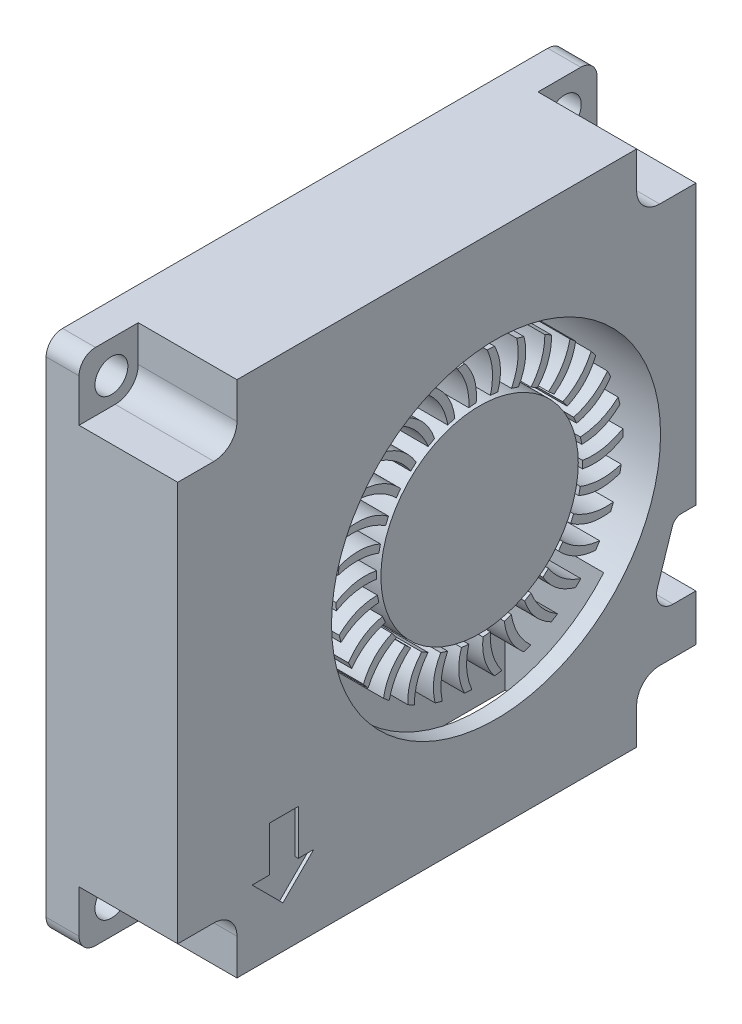
SolidWorks part; units mm, degrees
material "PPE"
ref_plane "Front Plane" through (0, 0, 0) normal (1, 0, 0) x (0, 1, 0)
ref_plane "Top Plane" through (0, 0, 0) normal (0, 0, 1) x (0, 1, 0)
ref_plane "Right Plane" through (0, 0, 0) normal (0, 1, 0) x (-1, 0, 0)
sketch "Sketch1" plane through (0, 0, 0) normal (1, 0, 0) x (0, 1, 0)
  line L1 (-18.73, -20) -> (18.73, -20)
  line L2 (-20, -18.73) -> (-20, 18.73)
  line L3 (-18.73, 20) -> (18.73, 20)
  line L4 (20, -18.73) -> (20, 18.73)
  line L5 (-20, -20) -> (20, 20) construction
  line L6 (-20, 20) -> (20, -20) construction
  arc A0 (-18.73, -20) -> (-20, -18.73) centre (-18.73, -18.73) cw
  arc A1 (-20, 18.73) -> (-18.73, 20) centre (-18.73, 18.73) cw
  arc A2 (18.73, -20) -> (20, -18.73) centre (18.73, -18.73) ccw
  arc A3 (18.73, 20) -> (20, 18.73) centre (18.73, 18.73) cw
  point P0 (0, 0)
  dimension "D2" = 1.27
  dimension "D1" = 40
extrude "Boss-Extrude1" add sketch "Sketch1" along normal blind 10.16
sketch "Sketch2" plane through (10.16, 0, 0) normal (1, 0, 0) x (0, 1, 0)
  line L2 (-20, 18.73) -> (-20, -18.73) construction
  line L3 (-24.572, 24.572) -> (-15.428, 24.572)
  line L4 (-24.572, 24.572) -> (-24.572, 15.428)
  line L5 (-24.572, 15.428) -> (-17.206, 15.428)
  line L6 (-15.428, 24.572) -> (-15.428, 17.206)
  line L7 (-24.572, 24.572) -> (-15.428, 15.428) construction
  line L8 (-24.572, 15.428) -> (-15.428, 24.572) construction
  line L9 (18.73, 20) -> (-18.73, 20) construction
  line L10 (24.572, 24.572) -> (15.428, 24.572)
  line L11 (24.572, 24.572) -> (24.572, 15.428)
  line L12 (24.572, 15.428) -> (17.206, 15.428)
  line L13 (15.428, 24.572) -> (15.428, 17.206)
  line L14 (24.572, -24.572) -> (24.572, -15.428)
  line L15 (24.572, -24.572) -> (15.428, -24.572)
  line L16 (15.428, -24.572) -> (15.428, -17.206)
  line L17 (24.572, -15.428) -> (17.206, -15.428)
  line L18 (-24.572, -24.572) -> (-15.428, -24.572)
  line L19 (-24.572, -24.572) -> (-24.572, -15.428)
  line L20 (-24.572, -15.428) -> (-17.206, -15.428)
  line L21 (-15.428, -24.572) -> (-15.428, -17.206)
  arc A4 (-17.206, 15.428) -> (-15.428, 17.206) centre (-17.206, 17.206) ccw
  arc A5 (15.428, 17.206) -> (17.206, 15.428) centre (17.206, 17.206) ccw
  arc A6 (17.206, -15.428) -> (15.428, -17.206) centre (17.206, -17.206) ccw
  arc A7 (-15.428, -17.206) -> (-17.206, -15.428) centre (-17.206, -17.206) ccw
  point P0 (-20, 20)
  point P5 (0, 0)
  point P15 (0, 0)
  point P35 (0, 0)
  dimension "D1" = 4.572
  dimension "D3" = 1.778
  dimension "D2" = 4.572
  dimension "D4" = 4
extrude "Cut-Extrude1" cut sketch "Sketch2" against normal blind 7.62
sketch "Sketch3" plane through (10.16, 0, 0) normal (1, 0, 0) x (0, 1, 0)
  circle A0 centre (0, -4.572) radius 12.7
  point P2 (-1.9961, -4.964)
  dimension "D3" = 25.4
  dimension "D1" = 4.572
  dimension "D2" = 0
extrude "Cut-Extrude2" cut sketch "Sketch3" against normal blind 8.89
sketch "Sketch4" plane through (0, -20, 0) normal (0, -1, 0) x (1, 0, 0)
  line L0 (10.16, 15.428) -> (10.16, -15.428) construction
  line L1 (1.27, 14.158) -> (8.89, 14.158)
  line L2 (1.27, 14.158) -> (1.27, -14.158)
  line L3 (1.27, -14.158) -> (8.89, -14.158)
  line L4 (8.89, 14.158) -> (8.89, -14.158)
  line L5 (0, 18.73) -> (0, -18.73) construction
  line L8 (10.16, 15.428) -> (2.54, 15.428) construction
  line L9 (2.54, -15.428) -> (10.16, -15.428) construction
  dimension "D1" = 1.27
  dimension "D2" = 1.27
  dimension "D3" = 1.27
  dimension "D4" = 1.27
extrude "Cut-Extrude3" cut sketch "Sketch4" against normal blind 36.576
sketch "Sketch5" plane through (1.27, 0, 0) normal (1, 0, 0) x (0, 1, 0)
  circle A0 centre (0, -4.572) radius 11.43
  dimension "D1" = 22.86
extrude "Boss-Extrude2" add sketch "Sketch5" along normal blind 1.27
sketch "Sketch6" plane through (2.54, 0, 0) normal (1, 0, 0) x (0, 1, 0)
  line L60 (-0.5633, 6.4855) -> (0, 6.507)
  line L61 (0, 3.375) -> (0.574, 3.375)
  line L62 (1.6523, 3.2014) -> (2.2137, 3.082)
  line L63 (1.748, 6.3609) -> (2.3035, 6.2649)
  line L64 (3.2324, 2.688) -> (3.7567, 2.4545)
  line L65 (3.9829, 5.7586) -> (4.5062, 5.5492)
  line L66 (4.6712, 1.8573) -> (5.1355, 1.5199)
  line L67 (6.0437, 4.7048) -> (6.5121, 4.3911)
  line L68 (5.9058, 0.7456) -> (6.2899, 0.3191)
  line L69 (7.8404, 3.2455) -> (8.2333, 2.8413)
  line L70 (6.8823, -0.5985) -> (7.1693, -1.0955)
  line L71 (9.2944, 1.4445) -> (9.5947, 0.9675)
  line L72 (7.5581, -2.1162) -> (7.7354, -2.6621)
  line L73 (10.3422, -0.6193) -> (10.5367, -1.1484)
  line L74 (7.9035, -3.7413) -> (7.9635, -4.3121)
  line L75 (10.938, -2.856) -> (11.0183, -3.4139)
  line L76 (7.9035, -5.4027) -> (7.8435, -5.9735)
  line L77 (11.0558, -5.1676) -> (11.0183, -5.7301)
  line L78 (7.5581, -7.0278) -> (7.3807, -7.5736)
  line L79 (10.6903, -7.4532) -> (10.5367, -7.9956)
  line L80 (6.8823, -8.5455) -> (6.5954, -9.0426)
  line L81 (9.8577, -9.6129) -> (9.5947, -10.1115)
  line L82 (5.9058, -9.8896) -> (5.5218, -10.3161)
  line L83 (8.5942, -11.5523) -> (8.2333, -11.9853)
  line L84 (4.6712, -11.0013) -> (4.2068, -11.3387)
  line L85 (6.9551, -13.1866) -> (6.5121, -13.5351)
  line L86 (3.2324, -11.832) -> (2.708, -12.0654)
  line L87 (5.0121, -14.4444) -> (4.5062, -14.6932)
  line L88 (1.6523, -12.3454) -> (1.0909, -12.4647)
  line L89 (2.8499, -15.2707) -> (2.3035, -15.4089)
  line L90 (0, -12.519) -> (-0.574, -12.519)
  line L91 (0.5633, -15.6295) -> (0, -15.651)
  line L92 (-1.6523, -12.3454) -> (-2.2137, -12.226)
  line L93 (-1.748, -15.5049) -> (-2.3035, -15.4089)
  line L94 (-3.2324, -11.832) -> (-3.7567, -11.5985)
  line L95 (-3.9829, -14.9026) -> (-4.5062, -14.6932)
  line L96 (-4.6712, -11.0013) -> (-5.1355, -10.6639)
  line L97 (-6.0437, -13.8488) -> (-6.5121, -13.5351)
  line L98 (-5.9058, -9.8896) -> (-6.2899, -9.4631)
  line L99 (-7.8404, -12.3895) -> (-8.2333, -11.9853)
  line L100 (-6.8823, -8.5455) -> (-7.1693, -8.0485)
  line L101 (-9.2944, -10.5885) -> (-9.5947, -10.1115)
  line L102 (-7.5581, -7.0278) -> (-7.7354, -6.4819)
  line L103 (-10.3422, -8.5247) -> (-10.5367, -7.9956)
  line L104 (-7.9035, -5.4027) -> (-7.9635, -4.8319)
  line L105 (-10.938, -6.288) -> (-11.0183, -5.7301)
  line L106 (-7.9035, -3.7413) -> (-7.8435, -3.1705)
  line L107 (-11.0558, -3.9764) -> (-11.0183, -3.4139)
  line L108 (-7.5581, -2.1162) -> (-7.3807, -1.5704)
  line L109 (-10.6903, -1.6908) -> (-10.5367, -1.1484)
  line L110 (-6.8823, -0.5985) -> (-6.5954, -0.1014)
  line L111 (-9.8577, 0.4689) -> (-9.5947, 0.9675)
  line L112 (-5.9058, 0.7456) -> (-5.5218, 1.1721)
  line L113 (-8.5942, 2.4083) -> (-8.2333, 2.8413)
  line L114 (-4.6712, 1.8573) -> (-4.2068, 2.1947)
  line L115 (-6.9551, 4.0426) -> (-6.5121, 4.3911)
  line L116 (-3.2324, 2.688) -> (-2.708, 2.9214)
  line L117 (-5.0121, 5.3004) -> (-4.5062, 5.5492)
  line L118 (-1.6523, 3.2014) -> (-1.0909, 3.3207)
  line L119 (-2.8499, 6.1267) -> (-2.3035, 6.2649)
  circle A3 centre (0, -4.572) radius 7.62
  circle A4 centre (0, -4.572) radius 11.43 construction
  spline S0 degree 2 poles (0, 3.375) (0.2617, 5.0251) (-0.5633, 6.4855) knots 0 0 0 1 1 1
  spline S1 degree 2 poles (0.574, 3.375) (0.9192, 5.0579) (0, 6.507) knots 0 0 0 1 1 1
  spline S2 degree 2 poles (2.2137, 3.082) (2.9012, 4.6563) (2.3035, 6.2649) knots 0 0 0 1 1 1
  spline S3 degree 2 poles (1.6523, 3.2014) (2.2513, 4.7609) (1.748, 6.3609) knots 0 0 0 1 1 1
  spline S4 degree 2 poles (3.7567, 2.4545) (4.7565, 3.8515) (4.5062, 5.5492) knots 0 0 0 1 1 1
  spline S5 degree 2 poles (3.2324, 2.688) (4.1425, 4.0889) (3.9829, 5.7586) knots 0 0 0 1 1 1
  spline S6 degree 2 poles (5.1355, 1.5199) (6.4039, 2.6784) (6.5121, 4.3911) knots 0 0 0 1 1 1
  spline S7 degree 2 poles (4.6712, 1.8573) (5.8527, 3.0384) (6.0437, 4.7048) knots 0 0 0 1 1 1
  spline S8 degree 2 poles (6.2899, 0.3191) (7.7714, 1.1886) (8.2333, 2.8413) knots 0 0 0 1 1 1
  spline S9 degree 2 poles (5.9058, 0.7456) (7.3071, 1.6552) (7.8404, 3.2455) knots 0 0 0 1 1 1
  spline S10 degree 2 poles (7.1693, -1.0955) (8.7993, -0.5531) (9.5947, 0.9675) knots 0 0 0 1 1 1
  spline S11 degree 2 poles (6.8823, -0.5985) (8.4421, -0.0001) (9.2944, 1.4445) knots 0 0 0 1 1 1
  spline S12 degree 2 poles (7.7354, -2.6621) (9.4426, -2.4704) (10.5367, -1.1484) knots 0 0 0 1 1 1
  spline S13 degree 2 poles (7.5581, -2.1162) (9.2082, -1.8552) (10.3422, -0.6193) knots 0 0 0 1 1 1
  spline S14 degree 2 poles (7.9635, -4.3121) (9.6732, -4.4795) (11.0183, -3.4139) knots 0 0 0 1 1 1
  spline S15 degree 2 poles (7.9035, -3.7413) (9.5718, -3.8291) (10.938, -2.856) knots 0 0 0 1 1 1
  spline S16 degree 2 poles (7.8435, -5.9735) (9.481, -6.4927) (11.0183, -5.7301) knots 0 0 0 1 1 1
  spline S17 degree 2 poles (7.9035, -5.4027) (9.5171, -5.8354) (11.0558, -5.1676) knots 0 0 0 1 1 1
  spline S18 degree 2 poles (7.3807, -7.5736) (8.8745, -8.422) (10.5367, -7.9956) knots 0 0 0 1 1 1
  spline S19 degree 2 poles (7.5581, -7.0278) (9.0465, -7.7865) (10.6903, -7.4532) knots 0 0 0 1 1 1
  spline S20 degree 2 poles (6.5954, -9.0426) (7.8801, -10.1829) (9.5947, -10.1115) knots 0 0 0 1 1 1
  spline S21 degree 2 poles (6.8823, -8.5455) (8.1805, -9.5972) (9.8577, -9.6129) knots 0 0 0 1 1 1
  spline S22 degree 2 poles (5.5218, -10.3161) (6.5413, -11.6987) (8.2333, -11.9853) knots 0 0 0 1 1 1
  spline S23 degree 2 poles (5.9058, -9.8896) (6.9569, -11.1882) (8.5942, -11.5523) knots 0 0 0 1 1 1
  spline S24 degree 2 poles (4.2068, -11.3387) (4.9167, -12.903) (6.5121, -13.5351) knots 0 0 0 1 1 1
  spline S25 degree 2 poles (4.6712, -11.0013) (5.4293, -12.49) (6.9551, -13.1866) knots 0 0 0 1 1 1
  spline S26 degree 2 poles (2.708, -12.0654) (3.0771, -13.7432) (4.5062, -14.6932) knots 0 0 0 1 1 1
  spline S27 degree 2 poles (3.2324, -11.832) (3.6644, -13.4458) (5.0121, -14.4444) knots 0 0 0 1 1 1
  spline S28 degree 2 poles (1.0909, -12.4647) (1.1031, -14.1825) (2.3035, -15.4089) knots 0 0 0 1 1 1
  spline S29 degree 2 poles (1.6523, -12.3454) (1.7394, -14.0137) (2.8499, -15.2707) knots 0 0 0 1 1 1
  spline S30 degree 2 poles (-0.574, -12.519) (-0.9192, -14.2019) (0, -15.651) knots 0 0 0 1 1 1
  spline S31 degree 2 poles (0, -12.519) (-0.2617, -14.1691) (0.5633, -15.6295) knots 0 0 0 1 1 1
  spline S32 degree 2 poles (-2.2137, -12.226) (-2.9012, -13.8003) (-2.3035, -15.4089) knots 0 0 0 1 1 1
  spline S33 degree 2 poles (-1.6523, -12.3454) (-2.2513, -13.9049) (-1.748, -15.5049) knots 0 0 0 1 1 1
  spline S34 degree 2 poles (-3.7567, -11.5985) (-4.7565, -12.9955) (-4.5062, -14.6932) knots 0 0 0 1 1 1
  spline S35 degree 2 poles (-3.2324, -11.832) (-4.1425, -13.2329) (-3.9829, -14.9026) knots 0 0 0 1 1 1
  spline S36 degree 2 poles (-5.1355, -10.6639) (-6.4039, -11.8224) (-6.5121, -13.5351) knots 0 0 0 1 1 1
  spline S37 degree 2 poles (-4.6712, -11.0013) (-5.8527, -12.1824) (-6.0437, -13.8488) knots 0 0 0 1 1 1
  spline S38 degree 2 poles (-6.2899, -9.4631) (-7.7714, -10.3326) (-8.2333, -11.9853) knots 0 0 0 1 1 1
  spline S39 degree 2 poles (-5.9058, -9.8896) (-7.3071, -10.7992) (-7.8404, -12.3895) knots 0 0 0 1 1 1
  spline S40 degree 2 poles (-7.1693, -8.0485) (-8.7993, -8.5909) (-9.5947, -10.1115) knots 0 0 0 1 1 1
  spline S41 degree 2 poles (-6.8823, -8.5455) (-8.4421, -9.1439) (-9.2944, -10.5885) knots 0 0 0 1 1 1
  spline S42 degree 2 poles (-7.7354, -6.4819) (-9.4426, -6.6736) (-10.5367, -7.9956) knots 0 0 0 1 1 1
  spline S43 degree 2 poles (-7.5581, -7.0278) (-9.2082, -7.2888) (-10.3422, -8.5247) knots 0 0 0 1 1 1
  spline S44 degree 2 poles (-7.9635, -4.8319) (-9.6732, -4.6645) (-11.0183, -5.7301) knots 0 0 0 1 1 1
  spline S45 degree 2 poles (-7.9035, -5.4027) (-9.5718, -5.3149) (-10.938, -6.288) knots 0 0 0 1 1 1
  spline S46 degree 2 poles (-7.8435, -3.1705) (-9.481, -2.6513) (-11.0183, -3.4139) knots 0 0 0 1 1 1
  spline S47 degree 2 poles (-7.9035, -3.7413) (-9.5171, -3.3086) (-11.0558, -3.9764) knots 0 0 0 1 1 1
  spline S48 degree 2 poles (-7.3807, -1.5704) (-8.8745, -0.722) (-10.5367, -1.1484) knots 0 0 0 1 1 1
  spline S49 degree 2 poles (-7.5581, -2.1162) (-9.0465, -1.3575) (-10.6903, -1.6908) knots 0 0 0 1 1 1
  spline S50 degree 2 poles (-6.5954, -0.1014) (-7.8801, 1.0389) (-9.5947, 0.9675) knots 0 0 0 1 1 1
  spline S51 degree 2 poles (-6.8823, -0.5985) (-8.1805, 0.4532) (-9.8577, 0.4689) knots 0 0 0 1 1 1
  spline S52 degree 2 poles (-5.5218, 1.1721) (-6.5413, 2.5547) (-8.2333, 2.8413) knots 0 0 0 1 1 1
  spline S53 degree 2 poles (-5.9058, 0.7456) (-6.9569, 2.0442) (-8.5942, 2.4083) knots 0 0 0 1 1 1
  spline S54 degree 2 poles (-4.2068, 2.1947) (-4.9167, 3.759) (-6.5121, 4.3911) knots 0 0 0 1 1 1
  spline S55 degree 2 poles (-4.6712, 1.8573) (-5.4293, 3.346) (-6.9551, 4.0426) knots 0 0 0 1 1 1
  spline S56 degree 2 poles (-2.708, 2.9214) (-3.0771, 4.5992) (-4.5062, 5.5492) knots 0 0 0 1 1 1
  spline S57 degree 2 poles (-3.2324, 2.688) (-3.6644, 4.3018) (-5.0121, 5.3004) knots 0 0 0 1 1 1
  spline S58 degree 2 poles (-1.0909, 3.3207) (-1.1031, 5.0385) (-2.3035, 6.2649) knots 0 0 0 1 1 1
  spline S59 degree 2 poles (-1.6523, 3.2014) (-1.7394, 4.8697) (-2.8499, 6.1267) knots 0 0 0 1 1 1
  dimension "D1" = 15.24
  dimension "D2" = 30
extrude "Boss-Extrude3" add sketch "Sketch6" along normal blind 6.35
sketch "Sketch7" plane through (10.16, 0, 0) normal (1, 0, 0) x (0, 1, 0)
  line L0 (-10.899, 12.9236) -> (-14.3717, 12.9236)
  line L1 (-14.3717, 12.9236) -> (-14.3717, 14.2593)
  line L2 (-14.3717, 14.2593) -> (-16.7492, 11.8818)
  line L3 (-16.7492, 11.8818) -> (-14.3717, 9.5043)
  line L4 (-14.3717, 9.5043) -> (-14.3717, 10.6931)
  line L5 (-14.3717, 10.6931) -> (-10.899, 10.6931)
  line L6 (-10.899, 10.6931) -> (-10.899, 12.9236)
extrude "Cut-Extrude4" cut sketch "Sketch7" against normal blind 0.254
sketch "Sketch8" plane through (10.16, 0, 0) normal (1, 0, 0) x (0, 1, 0)
  line L0 (-11.8357, -20) -> (-11.8357, -18.2328)
  line L1 (-15.428, -20) -> (15.428, -20) construction
  line L2 (-10.1726, -17.0252) -> (-6.6314, -18.1778)
  line L3 (-6.1053, -18.9024) -> (-6.1053, -20)
  line L4 (-6.1053, -20) -> (-11.8357, -20)
  arc A0 (-11.8357, -18.2328) -> (-10.1726, -17.0252) centre (-10.5657, -18.2328) cw
  arc A1 (-6.6314, -18.1778) -> (-6.1053, -18.9024) centre (-6.8673, -18.9024) cw
  dimension "D1" = 1.27
  dimension "D2" = 0.762
extrude "Cut-Extrude5" cut sketch "Sketch8" against normal blind 7.62
sketch "Sketch9" plane through (0, 0, 0) normal (-1, 0, 0) x (0, -1, 0)
  circle A0 centre (-17.5, 17.5) radius 1.27
  circle A1 centre (-17.5, 17.5) radius 1.27
  circle A2 centre (-17.5, 17.5) radius 1.27
  circle A3 centre (-17.5, 17.5) radius 1.27
  circle A4 centre (17.5, 17.5) radius 1.27
  circle A5 centre (17.5, -17.5) radius 1.27
  circle A6 centre (-17.5, -17.5) radius 1.27
  point P2 (0, 0)
  point P18 (0, 0)
  dimension "D3" = 2.54
  dimension "D1" = 17.5
  dimension "D2" = 17.5
  dimension "D4" = 4
  dimension "D5" = 4
extrude "Cut-Extrude6" cut sketch "Sketch9" against normal through all and the other way through all contours A4 | A5 | A6 | A0
